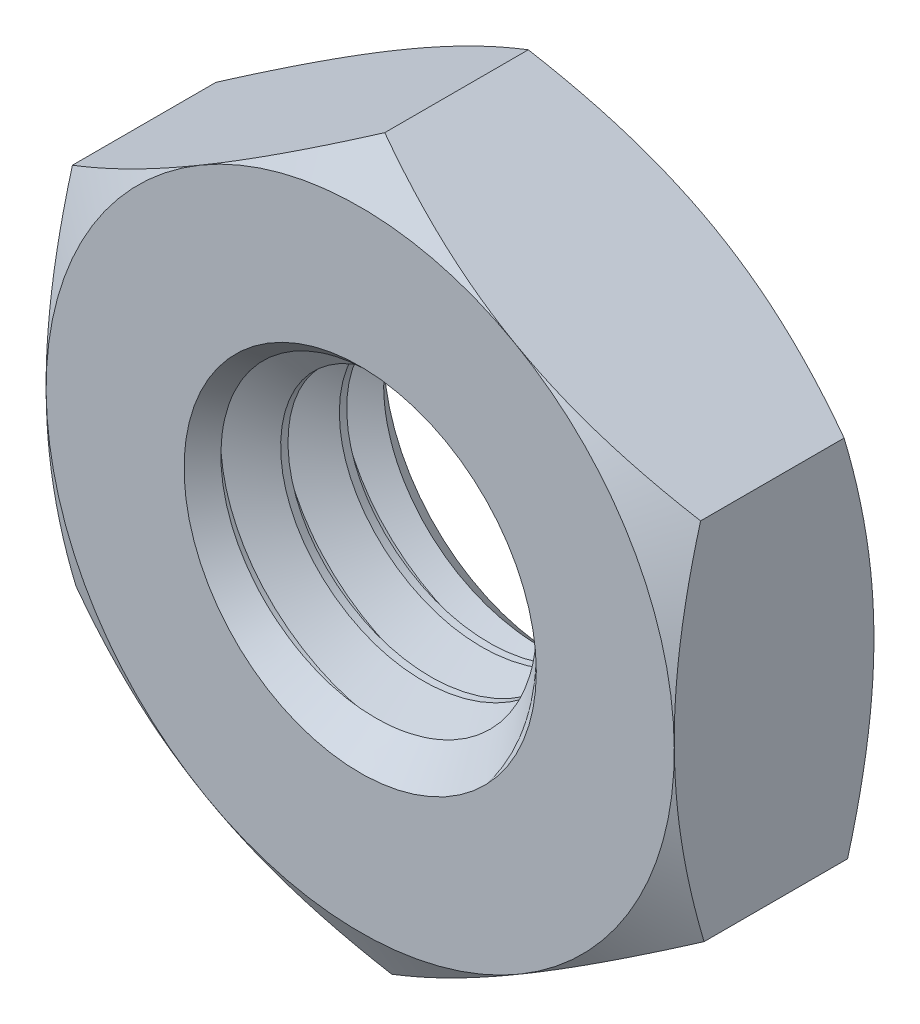
SolidWorks part; units mm, degrees
material "AISI 316 Annealed Stainless Steel Bar (SS)"
ref_plane "Front Plane" through (0, 0, 0) normal (0, 0, 1) x (1, 0, 0)
ref_plane "Top Plane" through (0, 0, 0) normal (0, 1, 0) x (1, 0, 0)
ref_plane "Right Plane" through (0, 0, 0) normal (1, 0, 0) x (0, 0, -1)
sketch "Sketch1" plane through (0, 0, 0) normal (0, 0, 1) x (1, 0, 0)
  line L0 (-2.6897, 1.5187) -> (-2.6601, -1.57)
  line L1 (-2.6601, -1.57) -> (0.0296, -3.0887)
  line L2 (0.0296, -3.0887) -> (2.6897, -1.5187)
  line L3 (2.6897, -1.5187) -> (2.6601, 1.57)
  line L4 (2.6601, 1.57) -> (-0.0296, 3.0887)
  line L5 (-0.0296, 3.0887) -> (-2.6897, 1.5187)
  circle A0 centre (0, 0) radius 1.5 construction
  circle A1 centre (0, 0) radius 2.675 construction
  dimension "nutBore" = 3
  dimension "D2" = 5.35
extrude "Base" add sketch "Sketch1" along normal mid plane 1.7
sketch "Sketch3" plane through (0, 0, 0.85) normal (0, 0, 1) x (1, 0, 0)
  circle A0 centre (0, 0) radius 2.675
extrude "Point roundings" cut sketch "Sketch3" against normal blind 1.7 draft 60 flip side to cut
sketch "Sketch10" plane through (0, 0, 0.85) normal (0, 0, 1) x (1, 0, 0)
  circle A0 centre (0, 0) radius 1.5
  dimension "D1" = 3
extrude "Funnel cut" cut sketch "Sketch10" against normal blind 0.85 draft 45
mirror "Mirror for point roundings" about plane through (0, 0, 0) normal (0, 0, 1) of "Funnel cut", "Point roundings"
sketch "Sketch4" plane through (0, 0, 0.85) normal (0, 0, 1) x (1, 0, 0)
  circle A0 centre (0, 0) radius 1.5
  dimension "D1" = 3
extrude "Plug" add sketch "Sketch4" against normal blind 1.7 separate body
sketch "Sketch5" plane through (0, 0, 0.85) normal (0, 0, 1) x (1, 0, 0)
  circle A0 centre (0, 0) radius 1.5
  dimension "D1" = 3
curve "Helix/Spiral1" pitch 0.5 height 3.4 radius 1.5 left hand yes centre (0, 0, 0.85) axis (0, 0, -1) start towards (1, 0, 0) parameters "nutPitch"=0.5
ref_point "Helix point"
sketch "Sketch7" plane through (0, 0, 0) normal (0, 1, 0) x (1, 0, 0)
  line L0 (1.5, -0.85) -> (1.5, -1.2875)
  line L1 (1.5, -1.2875) -> (1.1752, -1.1)
  line L2 (1.1752, -1.1) -> (1.1752, -1.0375)
  line L3 (1.1752, -1.0375) -> (1.5, -0.85)
  line L4 (1.3376, -1.1937) -> (1.3376, -0.9437) construction
  line L5 (1.5, -1.0687) -> (1.1752, -1.0687) construction
  line L7 (1.3152, -0.85) -> (2.6749, -0.85) construction
  dimension "D1" = 60
  dimension "D3" = 0.0625
  dimension "D2" = 0.25
  dimension "D4" = 0
sweep "Sweep cut" cut profiles "Sketch7" path "Helix/Spiral1" align with end faces yes
combine bodies "Combine" operation type subtract main body 108 bodies to subtract 117
equation "\"D1@Point roundings\" = \"nutThickness@Base\""
equation "\"D1@Sketch10\" = \"nutBore@Sketch1\""
equation "\"D1@Sketch4\" = \"nutBore@Sketch1\""
equation "\"D1@Plug\"=\"nutThickness@Base\""
equation "\"D1@Sketch5\" = \"nutBore@Sketch1\""
equation "\"D3@Helix/Spiral1\"=2*\"nutThickness@Base\""
equation "\"D3@Sketch7\"=1/8*\"nutPitch@Helix/Spiral1\""
equation "\"D2@Sketch7\"=1/2*\"nutPitch@Helix/Spiral1\""
equation "\"D1@Funnel cut\"=1/2*\"nutThickness@Base\""
